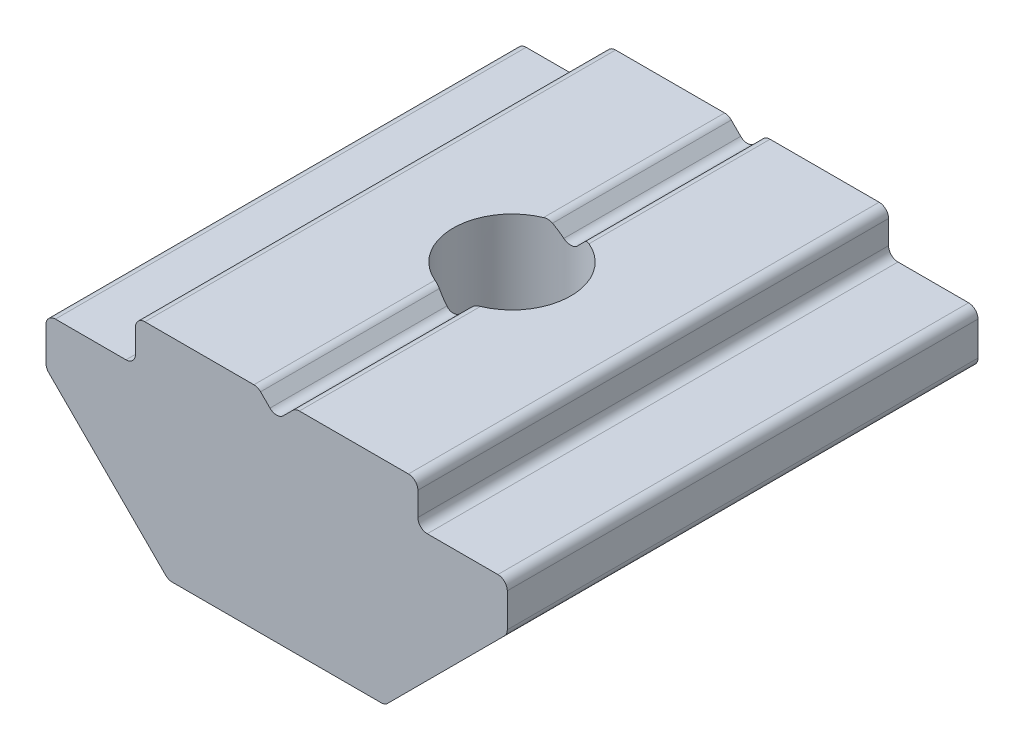
SolidWorks part; units mm, degrees
ref_plane "Front Plane" through (0, 0, 0) normal (0, 0, 1) x (1, 0, 0)
ref_plane "Top Plane" through (0, 0, 0) normal (0, 1, 0) x (1, 0, 0)
ref_plane "Right Plane" through (0, 0, 0) normal (1, 0, 0) x (0, 0, -1)
ref_plane "Plane1" through (0, 0, 5) normal (0, 0, 1) x (1, 0, 0)
sketch "Sketch1" plane through (0, 0, 5) normal (0, 0, 1) x (1, 0, 0)
  line L0 (4.9, -1) -> (4.9, 0.9)
  line L1 (4.9, 0.9) -> (-4.9, 0.9)
  line L2 (-4.9, 0.9) -> (-4.9, -1)
  line L3 (-4.9, -1) -> (-2.3, -3.6)
  line L4 (-2.3, -3.6) -> (2.3, -3.6)
  line L5 (2.3, -3.6) -> (4.9, -1)
extrude "Boss-Extrude1" add sketch "Sketch1" against normal blind 10
sketch "Sketch2" plane through (0, 0, -5) normal (0, 0, -1) x (-1, 0, 0)
  line L0 (4.9, 0.9) -> (3, 0.9)
  line L1 (3, 0.9) -> (3, 0)
  line L2 (3, 0) -> (4.9, 0)
  line L3 (4.9, 0) -> (4.9, 0.9)
extrude "Cut-Extrude1" cut sketch "Sketch2" against normal through all
sketch "Sketch3" plane through (0, 0, -5) normal (0, 0, -1) x (-1, 0, 0)
  line L0 (-4.9, 0) -> (-3, 0)
  line L1 (-3, 0) -> (-3, 0.9)
  line L2 (-3, 0.9) -> (-4.9, 0.9)
  line L3 (-4.9, 0.9) -> (-4.9, 0)
extrude "Cut-Extrude2" cut sketch "Sketch3" against normal through all
sketch "Sketch4" plane through (0, 0, -5) normal (0, 0, -1) x (-1, 0, 0)
  line L0 (0.4, 0.9) -> (-0.4, 0.9)
  line L1 (-0.4, 0.9) -> (0, 0.5)
  line L2 (0, 0.5) -> (0.4, 0.9)
extrude "Cut-Extrude3" cut sketch "Sketch4" against normal through all
hole_wizard "Ø4.2 (4.2) Diameter Hole1" positions "Sketch6" profile "Sketch5" hole size "Ø4.2" standard "ANSI Metric"
sketch "Sketch6" plane through (0, -3.6, 0) normal (0, -1, 0) x (-1, 0, 0)
  point P0 (0, 0)
sketch "Sketch5" plane through (0, -3.6, 0) normal (1, 0, 0) x (0, 0, -1)
  line L0 (0, 0) -> (0, 4.5)
  line L1 (0, 4.5) -> (1.25, 4.5)
  line L2 (1.25, 4.5) -> (1.25, 0)
  line L5 (1.25, 0) -> (0, 0)
  line L11 (0, -6.35) -> (0, 107.95) construction
  dimension "Thru Hole Dia." = 2.5
  dimension "Thru Hole Depth" = 4.5
fillet "Fillet1" radius 0.2 16 edges at (4.9, 0, 0) (3, 0, 0) (-4.9, -1, 0) (3, 0.9, 0) (-3, 0, 0) (0.4, 0.9, -3.0921) (0, 0.5, 3.125) (-0.4, 0.9, -3.0921) (4.9, -1, 0) (-3, 0.9, 0) (0, 0.5, -3.125) (-0.4, 0.9, 3.0921) (-4.9, 0, 0) (-2.3, -3.6, 0) (0.4, 0.9, 3.0921) (2.3, -3.6, 0) tangent propagation no
